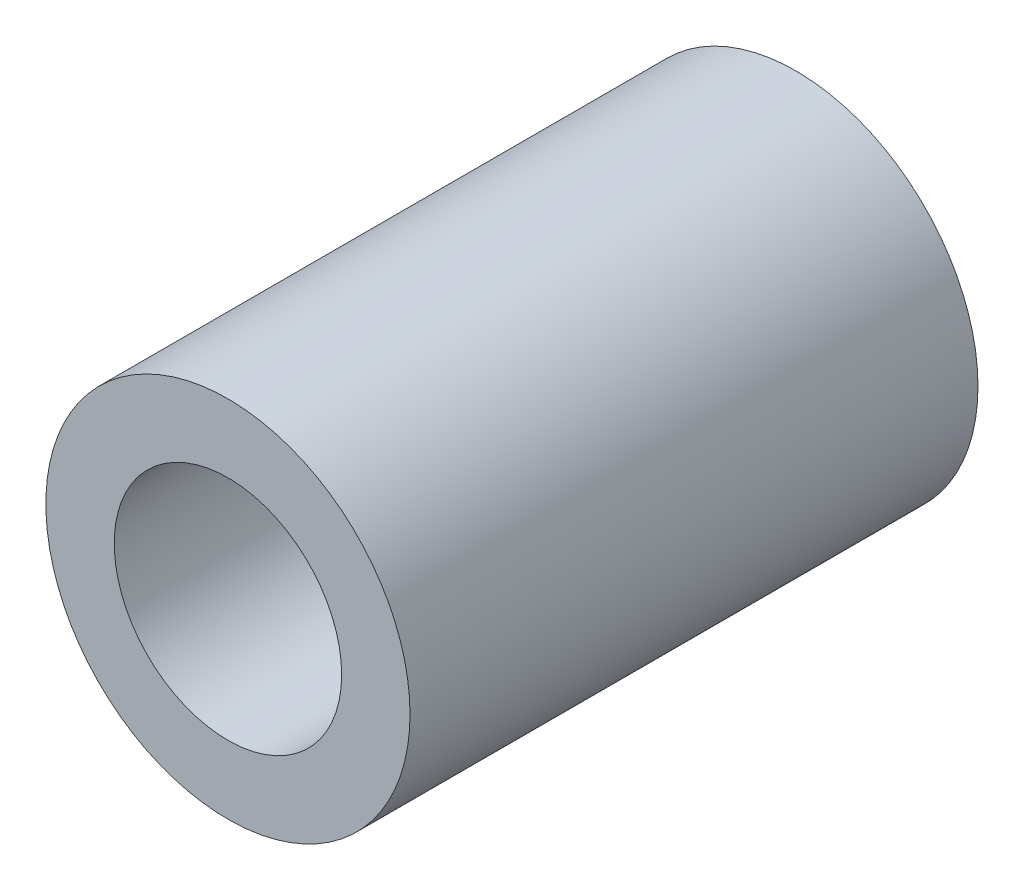
SolidWorks part; units mm, degrees
ref_plane "Front Plane" through (0, 0, 0) normal (0, 0, 1) x (1, 0, 0)
ref_plane "Top Plane" through (0, 0, 0) normal (0, 1, 0) x (1, 0, 0)
ref_plane "Right Plane" through (0, 0, 0) normal (1, 0, 0) x (0, 0, -1)
sketch "Sketch0" plane through (0, 0, 0) normal (1, 0, 0) x (0, 0, -1)
  line L0 (-12.5, 0) -> (12.5, 0) construction
  line L1 (-12.5, 0) -> (-12.5, 8.015) construction
  line L2 (-12.5, 8.015) -> (12.5, 8.015) construction
  line L3 (12.5, 8.015) -> (12.5, 0) construction
  line L4 (-12.5, -8.015) -> (-12.5, 8.015) construction
  line L5 (-12.5, 5.005) -> (-12.5, -5.005) construction
  line L6 (-12.5, 5.005) -> (12.5, 5.005) construction
  point P2 (0, 0)
  point P8 (-12.5, 0)
  point P9 (-12.5, 0)
  point P11 (-12.5, 5.005)
  point P12 (-12.5, -5.005)
  point P15 (12.5, 8.015)
  point P17 (-12.5, 8.015)
  dimension "Length" = 25
  dimension "OD" = 16.03
  dimension "ID" = 10.01
sketch "Sketch2" plane through (0, 0, 0) normal (0, 0, 1) x (1, 0, 0)
  line L2 (0, 5.005) -> (0, -5.005) construction
  line L3 (-5.005, 0) -> (5.005, 0) construction
  line L4 (-8.015, 0) -> (8.015, 0) construction
  circle A3 centre (0, 0) radius 8.015
  circle A4 centre (0, 0) radius 5.005
  dimension "ID Tol" = 10.01
  dimension "OD Tol" = 16.03
sketch "Sketch5" plane through (0, 0, 0) normal (1, 0, 0) x (0, 0, -1)
  line L1 (-12.5, 8.015) -> (12.5, 8.015)
  line L2 (-12.5, 8.015) -> (-12.5, 5.005)
  line L3 (-12.5, 5.005) -> (12.5, 5.005)
  line L4 (12.5, 8.015) -> (12.5, 5.005)
revolve "Revolve1" add sketch "Sketch5" angle 360 about L0
ref_axis "Center Axis 1" through (0, 0, -12.5) along (0, 0, 1)
